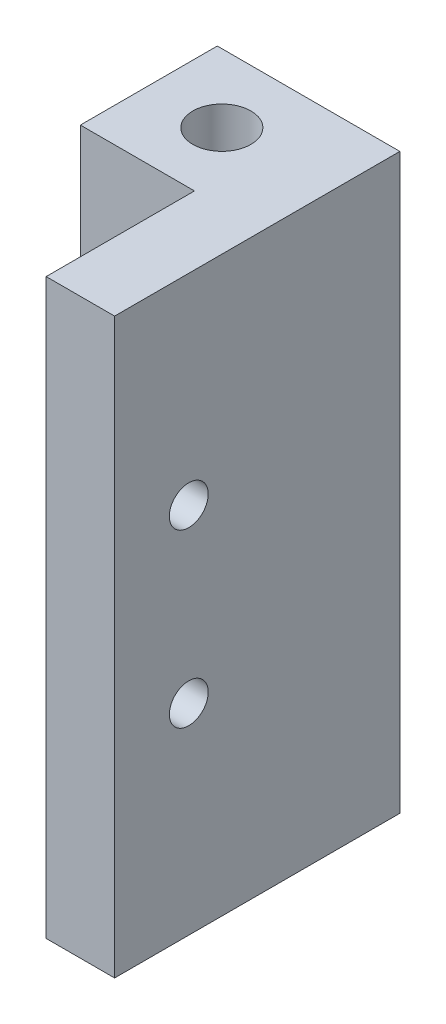
SolidWorks part; units mm, degrees
material "PET"
ref_plane "Front" through (0, 0, 0) normal (0, 0, 1) x (1, 0, 0)
ref_plane "Top" through (0, 0, 0) normal (0, 1, 0) x (1, 0, 0)
ref_plane "Right" through (0, 0, 0) normal (1, 0, 0) x (0, 0, -1)
sketch "Sketch1" plane through (0, 0, 0) normal (0, 1, 0) x (1, 0, 0)
  line L0 (0, 0) -> (-7.9375, 0)
  line L1 (-7.9375, 0) -> (-7.9375, 9.525)
  line L2 (-7.9375, 9.525) -> (4.7625, 9.525)
  line L3 (4.7625, 9.525) -> (4.7625, -10.3187)
  line L4 (4.7625, -10.3187) -> (0, -10.3187)
  line L5 (0, -10.3187) -> (0, 0)
  circle A0 centre (0, 4.7625) radius 2.0193 construction
  point P9 (0, 0)
  point P10 (0, 0)
  dimension "D5" = 4.0386
  dimension "D1" = 2.7432
  dimension "D2" = 9.525
  dimension "D3" = 19.8438
  dimension "D4" = 4.7625
  dimension "D6" = 12.7
extrude "Boss-Extrude1" add sketch "Sketch1" along normal blind 39.878
sketch "Sketch6" plane through (0, 39.878, 0) normal (0, 1, 0) x (1, 0, 0)
  line L16 (4.7625, 9.525) -> (-7.9375, 9.525) construction
  line L17 (-7.9375, 9.525) -> (-7.9375, 0) construction
  point P0 (-2.8575, 4.7625)
  dimension "D1" = 4.7625
  dimension "D2" = 5.08
hole_wizard "#10-32 Tapped Hole1" positions "Sketch6" profile "Sketch5" tap size "#10-32" standard "ANSI Inch" end condition up to next
sketch "Sketch5" plane through (-2.8575, 39.878, -4.7625) normal (1, 0, 0) x (0, 0, 1)
  line L0 (0, 0) -> (0, 39.878)
  line L1 (0, 39.878) -> (2.0193, 39.878)
  line L2 (2.0193, 39.878) -> (2.0193, 0)
  line L5 (2.0193, 0) -> (0, 0)
  line L11 (0, -6.35) -> (0, 107.95) construction
  dimension "Thru Tap Drill Dia." = 4.0386
  dimension "Thru Tap Drill Depth" = 39.878
cosmetic thread "Hole Thread1" parameters "D2"=4.826
sketch "Sketch9" plane through (0, 0, 0) normal (-1, 0, 0) x (0, 0, 1)
  line L0 (0, 39.878) -> (10.3187, 39.878) construction
  line L1 (0, 25.9055) -> (5.1594, 25.9055) construction
  line L2 (0, 39.878) -> (0, 0) construction
  line L3 (5.1594, 25.9055) -> (10.3188, 25.9055) construction
  line L4 (10.3187, 39.878) -> (10.3187, 0) construction
  line L5 (0, 0) -> (10.3187, 0) construction
  point P0 (5.1594, 25.9055)
  point P19 (5.1594, 13.9725)
  point P22 (0, 0)
  dimension "D1" = 13.9725
  dimension "D2" = 13.9725
hole_wizard "#6-32 Tapped Hole1" positions "Sketch9" profile "Sketch8" tap size "#6-32" standard "ANSI Inch" end condition up to next
sketch "Sketch8" plane through (0, 25.9055, 5.1594) normal (0, 1, 0) x (0, 0, 1)
  line L0 (0, 0) -> (0, 4.7625)
  line L1 (0, 4.7625) -> (1.3525, 4.7625)
  line L2 (1.3525, 4.7625) -> (1.3525, 0)
  line L5 (1.3525, 0) -> (0, 0)
  line L11 (0, -6.35) -> (0, 107.95) construction
  dimension "Thru Tap Drill Dia." = 2.7051
  dimension "Thru Tap Drill Depth" = 4.7625
cosmetic thread "Hole Thread2" parameters "D2"=3.5052
cosmetic thread "Hole Thread3" parameters "D2"=3.5052
